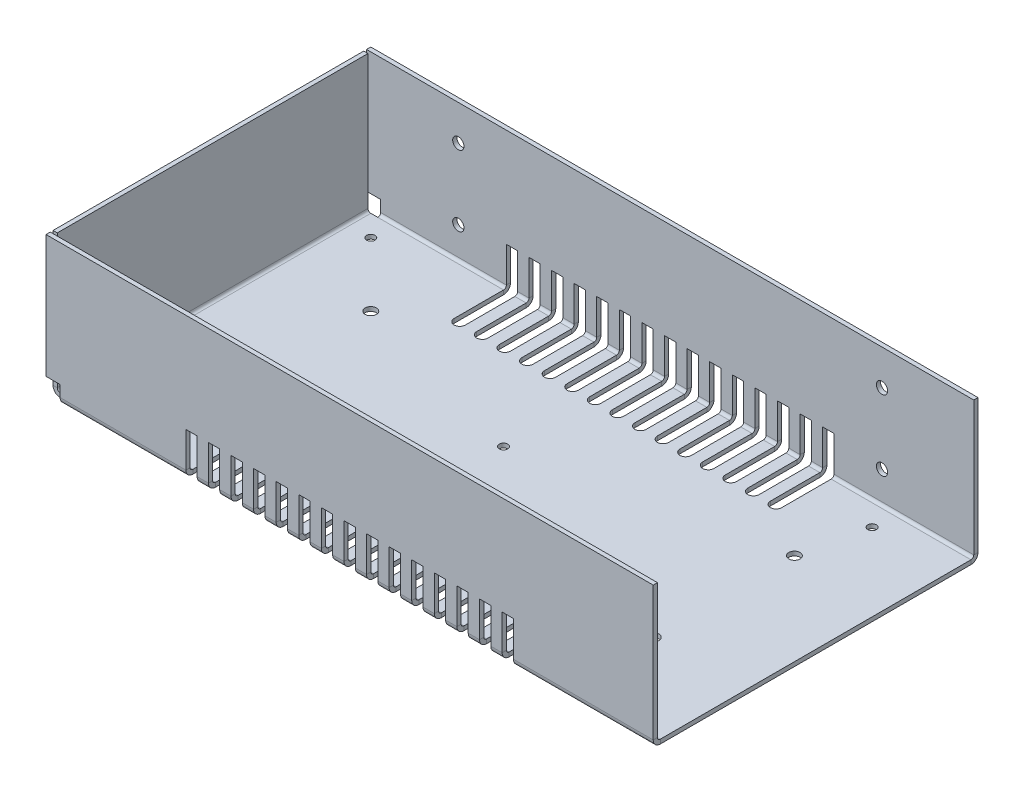
SolidWorks part; units mm, degrees
note: The reader was unsure of these and kept them because the rebuilt part matched: thickness of "基体-法兰1", "边线-法兰1", "边线-法兰4", "边线-法兰5", "钣金6", "钣金7", "钣金14", "钣金16", "钣金17", "钣金18", "钣金19", "钣金20", "钣金21"; flange length of "边线-法兰1", "边线-法兰4", "边线-法兰5".
ref_plane "前视基准面" through (0, 0, 0) normal (0, 0, 1) x (1, 0, 0)
ref_plane "上视基准面" through (0, 0, 0) normal (0, 1, 0) x (1, 0, 0)
ref_plane "右视基准面" through (0, 0, 0) normal (1, 0, 0) x (0, 0, -1)
other "Configuration Table"
sketch "草图1" plane through (0, 0, 0) normal (0, 1, 0) x (1, 0, 0)
  line L1 (-107.5, -57.5) -> (107.5, -57.5)
  line L2 (-107.5, -57.5) -> (-107.5, 57.5)
  line L3 (-107.5, 57.5) -> (107.5, 57.5)
  line L4 (107.5, -57.5) -> (107.5, 57.5)
  line L5 (-107.5, -57.5) -> (107.5, 57.5) construction
  line L6 (-107.5, 57.5) -> (107.5, -57.5) construction
  point P0 (0, 0)
  dimension "D1" = 215
  dimension "D2" = 115
base flange "基体-法兰1" sketch "草图1" thickness 1.5 reverse thickness direction no parameters "D1"=0.7366
edge flange "边线-法兰1" sketch "草图8" flange angle 90 flange length 50 bend radius 1 thickness 1.5 relief rectangular parameters "D6"=10
sketch "草图8" plane through (0, 0, -57.5) normal (0, 0, -1) x (-1, 0, 0)
  line L0 (-107.5, 0) -> (107.5, 0) construction
  line L1 (-107.5, 0) -> (107.5, 0)
  line L2 (-107.5, 0) -> (-107.5, 48.5)
  line L3 (-107.5, 48.5) -> (107.5, 48.5)
  line L4 (107.5, 48.5) -> (107.5, 0)
  line L5 (-107.5, -1.5) -> (107.5, -1.5) construction
  dimension "D1" = 50
bend "边线折弯1" bend radius 1 bend angle 90 parameters "D5"=1
sketch "草图12" plane through (0, 0, 0) normal (0, 0, 1) x (1, 0, 0)
  line L1 (-107.5, -3) -> (-102.5, -3)
  line L2 (-107.5, -3) -> (-107.5, 5)
  line L3 (-107.5, 5) -> (-102.5, 5)
  line L4 (-102.5, -3) -> (-102.5, 5)
  dimension "D1" = 8
  dimension "D2" = 5
extrude "切除-拉伸7" cut sketch "草图12" against normal up to surface (2.5 mm away) from vertex at -55 contours L2 L1 L4 L3 up to face at (0, 24.75, -57.5)
edge flange "边线-法兰4" sketch "草图23" flange angle 90 flange length 50 bend radius 1 thickness 1.5 relief rectangular parameters "D6"=10
sketch "草图23" plane through (0, 0, 57.5) normal (0, 0, 1) x (1, 0, 0)
  line L0 (-107.5, 0) -> (107.5, 0) construction
  line L1 (-107.5, 0) -> (107.5, 0)
  line L2 (-107.5, 0) -> (-107.5, 48.5)
  line L3 (-107.5, 48.5) -> (107.5, 48.5)
  line L4 (107.5, 48.5) -> (107.5, 0)
  line L5 (-107.5, 48.5) -> (107.5, 48.5) construction
bend "边线折弯4" bend radius 1 bend angle 90 parameters "D5"=2
sketch "草图24" plane through (0, 0, 0) normal (0, 0, 1) x (1, 0, 0)
  line L4 (-107.5, -3) -> (-102.5, -3)
  line L5 (-102.5, -3) -> (-102.5, 5)
  line L6 (-102.5, 5) -> (-107.5, 5)
  line L7 (-107.5, 5) -> (-107.5, -3)
  line L8 (-107.5, -3) -> (-102.5, -3)
  line L9 (-102.5, -3) -> (-102.5, 5)
  line L10 (-102.5, 5) -> (-107.5, 5)
  line L11 (-107.5, 5) -> (-107.5, -3)
  dimension "D1" = 0
extrude "切除-拉伸8" cut sketch "草图24" along normal up to surface (2.5 mm away) from vertex at 55 up to face at (0, 24.75, 57.5)
edge flange "边线-法兰5" sketch "草图27" flange angle 90 flange length 50 bend radius 1 thickness 1.5 relief rectangular parameters "D6"=10
sketch "草图27" plane through (-107.5, 0, 0) normal (-1, 0, 0) x (0, 0, 1)
  line L0 (-55, 0) -> (55, 0) construction
  line L1 (-55, 0) -> (55, 0)
  line L2 (-55, 0) -> (-55, 48.5)
  line L3 (-55, 48.5) -> (55, 48.5)
  line L4 (55, 48.5) -> (55, 0)
  line L5 (57.5, 48.5) -> (56, 48.5) construction
bend "边线折弯5" bend radius 1 bend angle 90 parameters "D5"=3
sketch "草图28" plane through (0, 0, 0) normal (0, 1, 0) x (1, 0, 0)
  line L0 (80, 57.5) -> (80, -57.5) construction
  line L1 (-102.5, 57.5) -> (107.5, 57.5) construction
  line L2 (107.5, -57.5) -> (-102.5, -57.5) construction
  line L3 (107.5, -55) -> (107.5, 55) construction
  line L4 (107.5, 47.5) -> (-107.5, 47.5) construction
  line L5 (-107.5, -55) -> (-107.5, 55) construction
  line L6 (-97.5, -57.5) -> (-97.5, 57.5) construction
  line L7 (-107.5, -47.5) -> (107.5, -47.5) construction
  line L8 (75, -57.5) -> (75, 57.5) construction
  line L9 (-107.5, 25) -> (107.5, 25) construction
  line L10 (-107.5, -25) -> (107.5, -25) construction
  line L11 (-75, -57.5) -> (-75, 57.5) construction
  line L12 (-107.5, 7) -> (107.5, 7) construction
  line L13 (-10, -57.5) -> (-10, 57.5) construction
  circle A0 centre (-10, 7) radius 1.5
  circle A1 centre (-75, -25) radius 2
  circle A2 centre (-75, 25) radius 2
  circle A3 centre (75, -25) radius 2
  circle A4 centre (75, 25) radius 2
  circle A5 centre (80, 47.5) radius 1.5
  circle A6 centre (80, -47.5) radius 1.5
  circle A7 centre (-97.5, -47.5) radius 1.5
  circle A8 centre (-97.5, 47.5) radius 1.5
  dimension "D11" = 3
  dimension "D12" = 4
  dimension "D13" = 4
  dimension "D14" = 4
  dimension "D15" = 4
  dimension "D16" = 3
  dimension "D17" = 3
  dimension "D18" = 3
  dimension "D19" = 3
  dimension "D1" = 27.5
  dimension "D2" = 10
  dimension "D3" = 177.5
  dimension "D4" = 95
  dimension "D5" = 32.5
  dimension "D6" = 32.5
  dimension "D7" = 50
  dimension "D8" = 150
  dimension "D9" = 50.5
  dimension "D10" = 117.5
extrude "切除-拉伸9" cut sketch "草图28" along normal up to surface (1.5 mm away) from surface at -1.5 up to face at (-33.3333, 0, 0) starting at face at (-33.3333, -1.5, 0)
sketch "草图29" plane through (0, 0, 0) normal (0, 0, 1) x (1, 0, 0)
  line L0 (75, 48.5) -> (75, -1.5) construction
  line L1 (-107.5, 48.5) -> (107.5, 48.5) construction
  line L2 (-102.5, -1.5) -> (107.5, -1.5) construction
  line L3 (107.5, 48.5) -> (107.5, 1) construction
  line L4 (-75, 48.5) -> (-75, -1.5) construction
  line L5 (107.5, 23.5) -> (-107.5, 23.5) construction
  line L6 (-107.5, 5) -> (-107.5, 48.5) construction
  line L7 (107.5, 36) -> (-107.5, 36) construction
  line L8 (-107.5, 11) -> (107.5, 11) construction
  circle A0 centre (75, 36) radius 2
  circle A1 centre (75, 11) radius 2
  circle A2 centre (-75, 36) radius 2
  circle A3 centre (-75, 11) radius 2
  dimension "D6" = 4
  dimension "D7" = 4
  dimension "D8" = 4
  dimension "D9" = 4
  dimension "D1" = 32.5
  dimension "D2" = 150
  dimension "D3" = 25
  dimension "D4" = 12.5
  dimension "D5" = 12.5
extrude "切除-拉伸10" cut sketch "草图29" against normal up to surface (1.5 mm away) from surface at -56 up to face at (-34.1667, 18.1667, -57.5) starting at face at (-34.1667, 18.1667, -56)
sketch "草图30" plane through (0, 0, 0) normal (0, 1, 0) x (1, 0, 0)
  line L0 (-1000, 0) -> (49000, 0) construction
  line L1 (0, -1000) -> (0, 49000) construction
  line L2 (0, -57.5) -> (0, -37.5) construction
  line L3 (107.5, -57.5) -> (-102.5, -57.5) construction
  line L4 (-2, -57.5) -> (-2, -37.5)
  line L5 (2, -57.5) -> (2, -37.5)
  line L6 (8, -57.5) -> (8, -37.5) construction
  line L7 (6, -57.5) -> (6, -37.5)
  line L8 (10, -57.5) -> (10, -37.5)
  line L9 (16, -57.5) -> (16, -37.5) construction
  line L10 (14, -57.5) -> (14, -37.5)
  line L11 (18, -57.5) -> (18, -37.5)
  line L12 (24, -57.5) -> (24, -37.5) construction
  line L13 (22, -57.5) -> (22, -37.5)
  line L14 (26, -57.5) -> (26, -37.5)
  line L15 (32, -57.5) -> (32, -37.5) construction
  line L16 (30, -57.5) -> (30, -37.5)
  line L17 (34, -57.5) -> (34, -37.5)
  line L18 (40, -57.5) -> (40, -37.5) construction
  line L19 (38, -57.5) -> (38, -37.5)
  line L20 (42, -57.5) -> (42, -37.5)
  line L21 (48, -57.5) -> (48, -37.5) construction
  line L22 (46, -57.5) -> (46, -37.5)
  line L23 (50, -57.5) -> (50, -37.5)
  line L24 (56, -57.5) -> (56, -37.5) construction
  line L25 (54, -57.5) -> (54, -37.5)
  line L26 (58, -57.5) -> (58, -37.5)
  line L27 (0, -57.5) -> (8, -57.5) construction
  line L28 (-8, -57.5) -> (-8, -37.5) construction
  line L29 (-10, -57.5) -> (-10, -37.5)
  line L30 (-6, -57.5) -> (-6, -37.5)
  line L31 (-16, -57.5) -> (-16, -37.5) construction
  line L32 (-18, -57.5) -> (-18, -37.5)
  line L33 (-14, -57.5) -> (-14, -37.5)
  line L34 (-24, -57.5) -> (-24, -37.5) construction
  line L35 (-26, -57.5) -> (-26, -37.5)
  line L36 (-22, -57.5) -> (-22, -37.5)
  line L37 (-32, -57.5) -> (-32, -37.5) construction
  line L38 (-34, -57.5) -> (-34, -37.5)
  line L39 (-30, -57.5) -> (-30, -37.5)
  line L40 (-40, -57.5) -> (-40, -37.5) construction
  line L41 (-42, -57.5) -> (-42, -37.5)
  line L42 (-38, -57.5) -> (-38, -37.5)
  line L43 (-48, -57.5) -> (-48, -37.5) construction
  line L44 (-50, -57.5) -> (-50, -37.5)
  line L45 (-46, -57.5) -> (-46, -37.5)
  line L46 (-56, -57.5) -> (-56, -37.5) construction
  line L47 (-58, -57.5) -> (-58, -37.5)
  line L48 (-54, -57.5) -> (-54, -37.5)
  line L49 (0, -57.5) -> (-8, -57.5) construction
  line L50 (-56, 57.5) -> (-56, 37.5) construction
  line L51 (-58, 57.5) -> (-58, 37.5)
  line L52 (-54, 57.5) -> (-54, 37.5)
  line L53 (-48, 57.5) -> (-48, 37.5) construction
  line L54 (-50, 57.5) -> (-50, 37.5)
  line L55 (-46, 57.5) -> (-46, 37.5)
  line L56 (-40, 57.5) -> (-40, 37.5) construction
  line L57 (-42, 57.5) -> (-42, 37.5)
  line L58 (-38, 57.5) -> (-38, 37.5)
  line L59 (-32, 57.5) -> (-32, 37.5) construction
  line L60 (-34, 57.5) -> (-34, 37.5)
  line L61 (-30, 57.5) -> (-30, 37.5)
  line L62 (-24, 57.5) -> (-24, 37.5) construction
  line L63 (-26, 57.5) -> (-26, 37.5)
  line L64 (-22, 57.5) -> (-22, 37.5)
  line L65 (-16, 57.5) -> (-16, 37.5) construction
  line L66 (-18, 57.5) -> (-18, 37.5)
  line L67 (-14, 57.5) -> (-14, 37.5)
  line L68 (-8, 57.5) -> (-8, 37.5) construction
  line L69 (-10, 57.5) -> (-10, 37.5)
  line L70 (-6, 57.5) -> (-6, 37.5)
  line L71 (0, 57.5) -> (0, 37.5) construction
  line L72 (-2, 57.5) -> (-2, 37.5)
  line L73 (2, 57.5) -> (2, 37.5)
  line L74 (8, 57.5) -> (8, 37.5) construction
  line L75 (6, 57.5) -> (6, 37.5)
  line L76 (10, 57.5) -> (10, 37.5)
  line L77 (16, 57.5) -> (16, 37.5) construction
  line L78 (14, 57.5) -> (14, 37.5)
  line L79 (18, 57.5) -> (18, 37.5)
  line L80 (24, 57.5) -> (24, 37.5) construction
  line L81 (22, 57.5) -> (22, 37.5)
  line L82 (26, 57.5) -> (26, 37.5)
  line L83 (32, 57.5) -> (32, 37.5) construction
  line L84 (30, 57.5) -> (30, 37.5)
  line L85 (34, 57.5) -> (34, 37.5)
  line L86 (48, 57.5) -> (48, 37.5) construction
  line L87 (46, 57.5) -> (46, 37.5)
  line L88 (50, 57.5) -> (50, 37.5)
  line L89 (40, 57.5) -> (40, 37.5) construction
  line L90 (38, 57.5) -> (38, 37.5)
  line L91 (42, 57.5) -> (42, 37.5)
  line L92 (56, 57.5) -> (56, 37.5) construction
  line L93 (54, 57.5) -> (54, 37.5)
  line L94 (58, 57.5) -> (58, 37.5)
  arc A0 (-2, -57.5) -> (2, -57.5) centre (0, -57.5) ccw
  arc A1 (2, -37.5) -> (-2, -37.5) centre (0, -37.5) ccw
  arc A2 (6, -57.5) -> (10, -57.5) centre (8, -57.5) ccw
  arc A3 (10, -37.5) -> (6, -37.5) centre (8, -37.5) ccw
  arc A4 (14, -57.5) -> (18, -57.5) centre (16, -57.5) ccw
  arc A5 (18, -37.5) -> (14, -37.5) centre (16, -37.5) ccw
  arc A6 (22, -57.5) -> (26, -57.5) centre (24, -57.5) ccw
  arc A7 (26, -37.5) -> (22, -37.5) centre (24, -37.5) ccw
  arc A8 (30, -57.5) -> (34, -57.5) centre (32, -57.5) ccw
  arc A9 (34, -37.5) -> (30, -37.5) centre (32, -37.5) ccw
  arc A10 (38, -57.5) -> (42, -57.5) centre (40, -57.5) ccw
  arc A11 (42, -37.5) -> (38, -37.5) centre (40, -37.5) ccw
  arc A12 (46, -57.5) -> (50, -57.5) centre (48, -57.5) ccw
  arc A13 (50, -37.5) -> (46, -37.5) centre (48, -37.5) ccw
  arc A14 (54, -57.5) -> (58, -57.5) centre (56, -57.5) ccw
  arc A15 (58, -37.5) -> (54, -37.5) centre (56, -37.5) ccw
  arc A16 (-10, -57.5) -> (-6, -57.5) centre (-8, -57.5) ccw
  arc A17 (-6, -37.5) -> (-10, -37.5) centre (-8, -37.5) ccw
  arc A18 (-18, -57.5) -> (-14, -57.5) centre (-16, -57.5) ccw
  arc A19 (-14, -37.5) -> (-18, -37.5) centre (-16, -37.5) ccw
  arc A20 (-26, -57.5) -> (-22, -57.5) centre (-24, -57.5) ccw
  arc A21 (-22, -37.5) -> (-26, -37.5) centre (-24, -37.5) ccw
  arc A22 (-34, -57.5) -> (-30, -57.5) centre (-32, -57.5) ccw
  arc A23 (-30, -37.5) -> (-34, -37.5) centre (-32, -37.5) ccw
  arc A24 (-42, -57.5) -> (-38, -57.5) centre (-40, -57.5) ccw
  arc A25 (-38, -37.5) -> (-42, -37.5) centre (-40, -37.5) ccw
  arc A26 (-50, -57.5) -> (-46, -57.5) centre (-48, -57.5) ccw
  arc A27 (-46, -37.5) -> (-50, -37.5) centre (-48, -37.5) ccw
  arc A28 (-58, -57.5) -> (-54, -57.5) centre (-56, -57.5) ccw
  arc A29 (-54, -37.5) -> (-58, -37.5) centre (-56, -37.5) ccw
  arc A30 (-58, 57.5) -> (-54, 57.5) centre (-56, 57.5) cw
  arc A31 (-54, 37.5) -> (-58, 37.5) centre (-56, 37.5) cw
  arc A32 (-50, 57.5) -> (-46, 57.5) centre (-48, 57.5) cw
  arc A33 (-46, 37.5) -> (-50, 37.5) centre (-48, 37.5) cw
  arc A34 (-42, 57.5) -> (-38, 57.5) centre (-40, 57.5) cw
  arc A35 (-38, 37.5) -> (-42, 37.5) centre (-40, 37.5) cw
  arc A36 (-34, 57.5) -> (-30, 57.5) centre (-32, 57.5) cw
  arc A37 (-30, 37.5) -> (-34, 37.5) centre (-32, 37.5) cw
  arc A38 (-26, 57.5) -> (-22, 57.5) centre (-24, 57.5) cw
  arc A39 (-22, 37.5) -> (-26, 37.5) centre (-24, 37.5) cw
  arc A40 (-18, 57.5) -> (-14, 57.5) centre (-16, 57.5) cw
  arc A41 (-14, 37.5) -> (-18, 37.5) centre (-16, 37.5) cw
  arc A42 (-10, 57.5) -> (-6, 57.5) centre (-8, 57.5) cw
  arc A43 (-6, 37.5) -> (-10, 37.5) centre (-8, 37.5) cw
  arc A44 (-2, 57.5) -> (2, 57.5) centre (0, 57.5) cw
  arc A45 (2, 37.5) -> (-2, 37.5) centre (0, 37.5) cw
  arc A46 (6, 57.5) -> (10, 57.5) centre (8, 57.5) cw
  arc A47 (10, 37.5) -> (6, 37.5) centre (8, 37.5) cw
  arc A48 (14, 57.5) -> (18, 57.5) centre (16, 57.5) cw
  arc A49 (18, 37.5) -> (14, 37.5) centre (16, 37.5) cw
  arc A50 (22, 57.5) -> (26, 57.5) centre (24, 57.5) cw
  arc A51 (26, 37.5) -> (22, 37.5) centre (24, 37.5) cw
  arc A52 (30, 57.5) -> (34, 57.5) centre (32, 57.5) cw
  arc A53 (34, 37.5) -> (30, 37.5) centre (32, 37.5) cw
  arc A54 (46, 57.5) -> (50, 57.5) centre (48, 57.5) cw
  arc A55 (50, 37.5) -> (46, 37.5) centre (48, 37.5) cw
  arc A56 (38, 57.5) -> (42, 57.5) centre (40, 57.5) cw
  arc A57 (42, 37.5) -> (38, 37.5) centre (40, 37.5) cw
  arc A58 (54, 57.5) -> (58, 57.5) centre (56, 57.5) cw
  arc A59 (58, 37.5) -> (54, 37.5) centre (56, 37.5) cw
  point P9 (0, -47.5)
  point P17 (8, -47.5)
  point P24 (16, -47.5)
  point P31 (24, -47.5)
  point P38 (32, -47.5)
  point P45 (40, -47.5)
  point P52 (48, -47.5)
  point P59 (56, -47.5)
  point P69 (-8, -47.5)
  point P76 (-16, -47.5)
  point P83 (-24, -47.5)
  point P90 (-32, -47.5)
  point P97 (-40, -47.5)
  point P104 (-48, -47.5)
  point P111 (-56, -47.5)
  point P118 (-56, 47.5)
  point P125 (-48, 47.5)
  point P132 (-40, 47.5)
  point P139 (-32, 47.5)
  point P146 (-24, 47.5)
  point P153 (-16, 47.5)
  point P160 (-8, 47.5)
  point P167 (0, 47.5)
  point P174 (8, 47.5)
  point P181 (16, 47.5)
  point P188 (24, 47.5)
  point P195 (32, 47.5)
  point P202 (48, 47.5)
  point P209 (40, 47.5)
  point P216 (56, 47.5)
  dimension "D2" = 2
  dimension "D1" = 20
  dimension "D4" = 8
  dimension "D6" = 8
  dimension "D3" = 8
  dimension "D5" = 8
extrude "切除-拉伸11" cut sketch "草图30" along normal blind 15 from surface at -1.5 starting at face at (-75, -1.5, 23)
sketch "折弯-线1" plane through (0, 0, 0) normal (0, 1, 0) x (1, 0, 0)
sketch "边界框1" plane through (0, 0, 0) normal (0, 1, 0) x (1, 0, 0)
sheet metal parameters "钣金6" thickness 1.5 parameters "D1"=0.7366
flat pattern "平板型式6" [suppressed]
sketch "折弯-线2" plane through (0, 0, 0) normal (0, 1, 0) x (1, 0, 0)
sketch "边界框2" [suppressed] plane through (0, 0, 0) normal (0, 1, 0) x (1, 0, 0)
sheet metal parameters "钣金7" thickness 1.5 parameters "D1"=0.7366, "D7"=3
flat pattern "平板型式6" [suppressed]
sketch "折弯-线2" plane through (0, 0, 0) normal (0, 1, 0) x (1, 0, 0)
sketch "边界框2" [suppressed] plane through (0, 0, 0) normal (0, 1, 0) x (1, 0, 0)
bend of the flat pattern "展平-<边线折弯1>1"
sheet metal parameters "钣金14" thickness 1.5 parameters "D1"=0.7366, "D7"=3
flat pattern "平板型式6" [suppressed]
sketch "折弯-线2" plane through (0, 0, 0) normal (0, 1, 0) x (1, 0, 0)
sketch "边界框2" [suppressed] plane through (0, 0, 0) normal (0, 1, 0) x (1, 0, 0)
bend of the flat pattern "展平-<边线折弯1>1"
bend of the flat pattern "展平-<边线折弯4>1"
sheet metal parameters "钣金16" thickness 1.5 parameters "D1"=0.7366, "D7"=3
flat pattern "平板型式6" [suppressed]
sketch "折弯-线2" plane through (0, 0, 0) normal (0, 1, 0) x (1, 0, 0)
sketch "边界框2" [suppressed] plane through (0, 0, 0) normal (0, 1, 0) x (1, 0, 0)
bend of the flat pattern "展平-<边线折弯1>1"
sheet metal parameters "钣金17" thickness 1.5 parameters "D1"=0.7366, "D7"=3
flat pattern "平板型式6" [suppressed]
sketch "折弯-线2" plane through (0, 0, 0) normal (0, 1, 0) x (1, 0, 0)
sketch "边界框2" [suppressed] plane through (0, 0, 0) normal (0, 1, 0) x (1, 0, 0)
bend of the flat pattern "展平-<边线折弯1>1"
bend of the flat pattern "展平-<边线折弯4>1"
sheet metal parameters "钣金18" thickness 1.5 parameters "D1"=0.7366, "D7"=3
flat pattern "平板型式6" [suppressed]
sketch "折弯-线2" plane through (0, 0, 0) normal (0, 1, 0) x (1, 0, 0)
sketch "边界框2" [suppressed] plane through (0, 0, 0) normal (0, 1, 0) x (1, 0, 0)
bend of the flat pattern "展平-<边线折弯1>1"
bend of the flat pattern "展平-<边线折弯4>1"
bend of the flat pattern "展平-<边线折弯5>1"
sheet metal parameters "钣金19" thickness 1.5 parameters "D1"=0.7366, "D7"=3
flat pattern "平板型式6" [suppressed]
sketch "折弯-线2" plane through (0, 0, 0) normal (0, 1, 0) x (1, 0, 0)
sketch "边界框2" [suppressed] plane through (0, 0, 0) normal (0, 1, 0) x (1, 0, 0)
bend of the flat pattern "展平-<边线折弯1>1"
bend of the flat pattern "展平-<边线折弯4>1"
bend of the flat pattern "展平-<边线折弯5>1"
sheet metal parameters "钣金20" thickness 1.5 parameters "D1"=0.7366, "D7"=3
flat pattern "平板型式6" [suppressed]
sketch "折弯-线2" plane through (0, 0, 0) normal (0, 1, 0) x (1, 0, 0)
sketch "边界框2" [suppressed] plane through (0, 0, 0) normal (0, 1, 0) x (1, 0, 0)
bend of the flat pattern "展平-<边线折弯1>1"
bend of the flat pattern "展平-<边线折弯4>1"
bend of the flat pattern "展平-<边线折弯5>1"
sheet metal parameters "钣金21" thickness 1.5 parameters "D1"=0.7366, "D7"=3
flat pattern "平板型式6" [suppressed]
sketch "折弯-线2" plane through (0, 0, 0) normal (0, 1, 0) x (1, 0, 0)
sketch "边界框2" [suppressed] plane through (0, 0, 0) normal (0, 1, 0) x (1, 0, 0)
bend of the flat pattern "展平-<边线折弯1>1"
bend of the flat pattern "展平-<边线折弯4>1"
bend of the flat pattern "展平-<边线折弯5>1"
